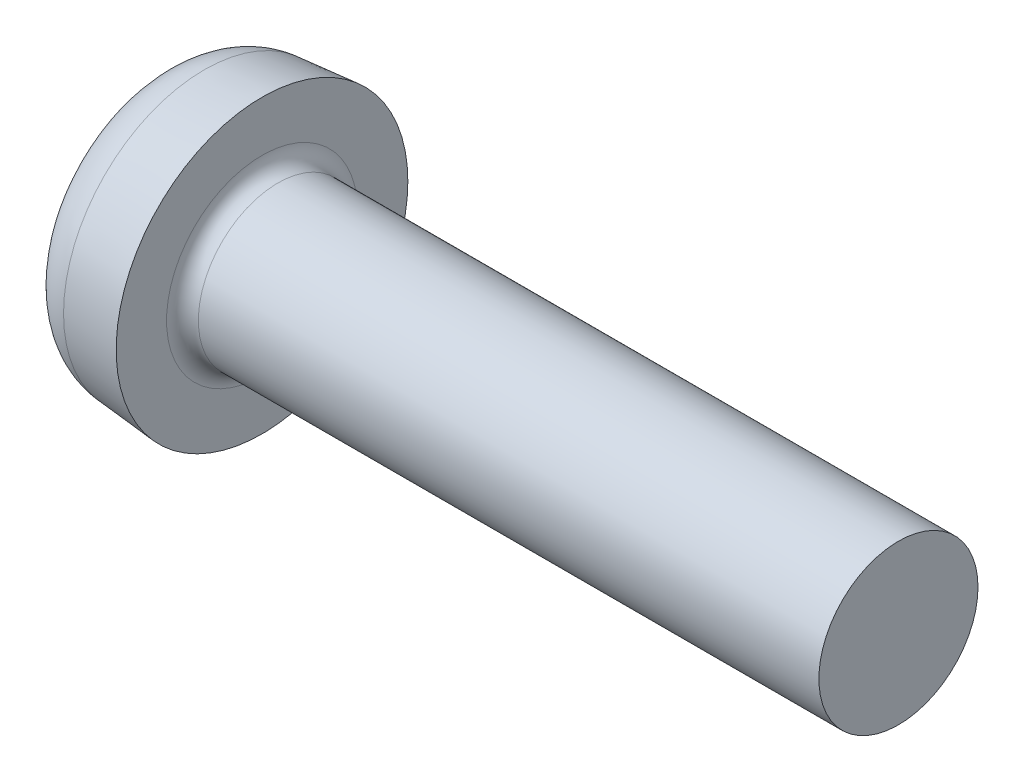
SolidWorks part; units mm, degrees
ref_plane "Front" through (0, 0, 0) normal (0, 0, 1) x (1, 0, 0)
ref_plane "Top" through (0, 0, 0) normal (0, 1, 0) x (1, 0, 0)
ref_plane "Right" through (0, 0, 0) normal (1, 0, 0) x (0, 0, -1)
sketch "Sketch1" plane through (0, 0, 0) normal (0, 0, 1) x (1, 0, 0)
  line L0 (14, 1.5) -> (3, 1.5)
  line L1 (2, 1.8) -> (2, 2.75)
  line L2 (2, 2.75) -> (0, 2.575)
  line L3 (3, 1.5) -> (2.3, 1.5)
  line L4 (14, 1.5) -> (14, 0)
  line L5 (4.5158, 0) -> (-13.5157, 0) construction
  line L6 (14, 0) -> (0, 0)
  line L7 (0, 0) -> (0, 2.575)
  arc A1 (2, 1.8) -> (2.3, 1.5) centre (2.3, 1.8) ccw
  dimension "D2" = 95
  dimension "k" = 2
  dimension "dk" = 5.5
revolve "Base" add sketch "Sketch1" angle 360 about L5
cosmetic thread "ThreadCosmetic1" parameters "bb"=12
sketch "Sketch6" plane through (0, 0, 0) normal (1, 0, 0) x (0, 0, -1)
  line L0 (-1.9271, 0) -> (2.0512, 0) construction
  line L1 (0, 1.8651) -> (0, -2.0207) construction
  line L2 (0.35, 0.35) -> (0.35, 1.75)
  line L3 (0.35, 1.75) -> (-0.35, 1.75)
  line L4 (-0.35, 0.35) -> (-0.35, 1.75)
  line L5 (0.35, 0.35) -> (1.75, 0.35)
  line L6 (1.75, 0.35) -> (1.75, -0.35)
  line L7 (-1.75, 0.35) -> (-1.75, -0.35)
  line L8 (-0.35, 0.35) -> (-1.75, 0.35)
  line L9 (-0.35, -0.35) -> (-1.75, -0.35)
  line L10 (0.35, -0.35) -> (1.75, -0.35)
  line L11 (-0.35, -0.35) -> (-0.35, -1.75)
  line L12 (0.35, -1.75) -> (-0.35, -1.75)
  line L13 (0.35, -0.35) -> (0.35, -1.75)
  point P16 (-1.75, 0)
  point P17 (1.75, 0)
extrude "CrossRecess" cut sketch "Sketch6" along normal blind 2
fillet "Fillet5" radius 0.3 4 edges at (1, -0.35, 0.35) (1, -0.35, -0.35) (1, 0.35, 0.35) (1, 0.35, -0.35)
sketch "Sketch8" [suppressed] plane through (0, 0, 0) normal (0, 0, 1) x (1, 0, 0)
  line L0 (12, 4) -> (8.2, 3.5)
  line L1 (8.2, 3.5) -> (5, 3.5)
  line L3 (50, -4) -> (50, 4) construction
  line L4 (5, -6.5) -> (5, 6.5) construction
  line L6 (5, 3.5) -> (5, 14)
  line L7 (5, 14) -> (12, 14)
  line L8 (12, 14) -> (12, 4)
  line L9 (52.4753, 0) -> (42.9594, 0) construction
  dimension "D1" = 23
fillet "HeadFillet" radius 1 1 edges at (0, 0, -2.575)
draft "Draft1" type of draft neutral plane draft angle 20 faces to draft 4 face at (1.004, -0.0875, 1.75) face at (1.004, -1.75, -0.0875) face at (1.004, 0.0875, -1.75) face at (1.004, 1.75, 0.0875) neutral plane through (0, 0, 0) neutral plane normal (-1, 0, 0) parameters "D1"=20
sketch "Sketch7" plane through (0, 0, 0) normal (1, 0, 0) x (0, 0, -1)
  line L0 (-8.3217, 0) -> (7.4212, 0) construction
  line L1 (0, 7.4989) -> (0, -7.9646) construction
  line L2 (0, 0) -> (6.8599, 6.8599) construction
  line L3 (1.2374, 1.2374) -> (0, 0.6604)
  line L4 (0, 0) -> (-6.8599, 6.8599) construction
  line L5 (1.2374, 1.2374) -> (0.6604, 0)
  line L6 (1.2374, -1.2374) -> (0, -0.6604)
  line L7 (1.2374, -1.2374) -> (0.6604, 0)
  line L8 (-1.2374, -1.2374) -> (0, -0.6604)
  line L9 (-1.2374, -1.2374) -> (-0.6604, 0)
  line L10 (-1.2374, 1.2374) -> (0, 0.6604)
  line L11 (-1.2374, 1.2374) -> (-0.6604, 0)
  dimension "D2" = 20
extrude "Cut-Extrude3" [suppressed] cut sketch "Sketch7" along normal blind 10 draft 20
sketch "Sketch10" plane through (0, 0, 0) normal (0, 0, 1) x (1, 0, 0)
  line L0 (14, 1.2657) -> (14.1353, 1.5)
  line L1 (14.1353, 1.5) -> (14.1353, 1.7705)
  line L2 (14.1353, 1.7705) -> (13.8648, 1.7705)
  line L3 (13.8648, 1.7705) -> (13.8648, 1.5)
  line L4 (13.8648, 1.5) -> (14, 1.2657)
  line L5 (14, 1.5) -> (3, 1.5) construction
  line L6 (14, 1.5) -> (14, 0) construction
  line L7 (0, 0) -> (57.111, 0) construction
  dimension "D1" = 0.2705
revolve "Cut-Revolve10" [suppressed] cut sketch "Sketch10" angle 360 about L7
pattern_linear "LPattern10" [suppressed] count 37 spacing 0.3246 along (-1, 0, 0) of bodies 107
equation "\"D1@Sketch6\" = \"m@Sketch6\" / 5"
equation "\"D1@Sketch8\" = \"d@Sketch8\" + 20"
equation "\"D1@Sketch10\" =  ( \"d@Sketch1\" - \"THD_MINOR@ThreadCosmetic1\" )  / 2"
equation "\"D3@LPattern10\" = \"D1@Sketch10\" * 1.2"
equation "\"D1@LPattern10\" = \"bb@ThreadCosmetic1\" / \"D3@LPattern10\" "
